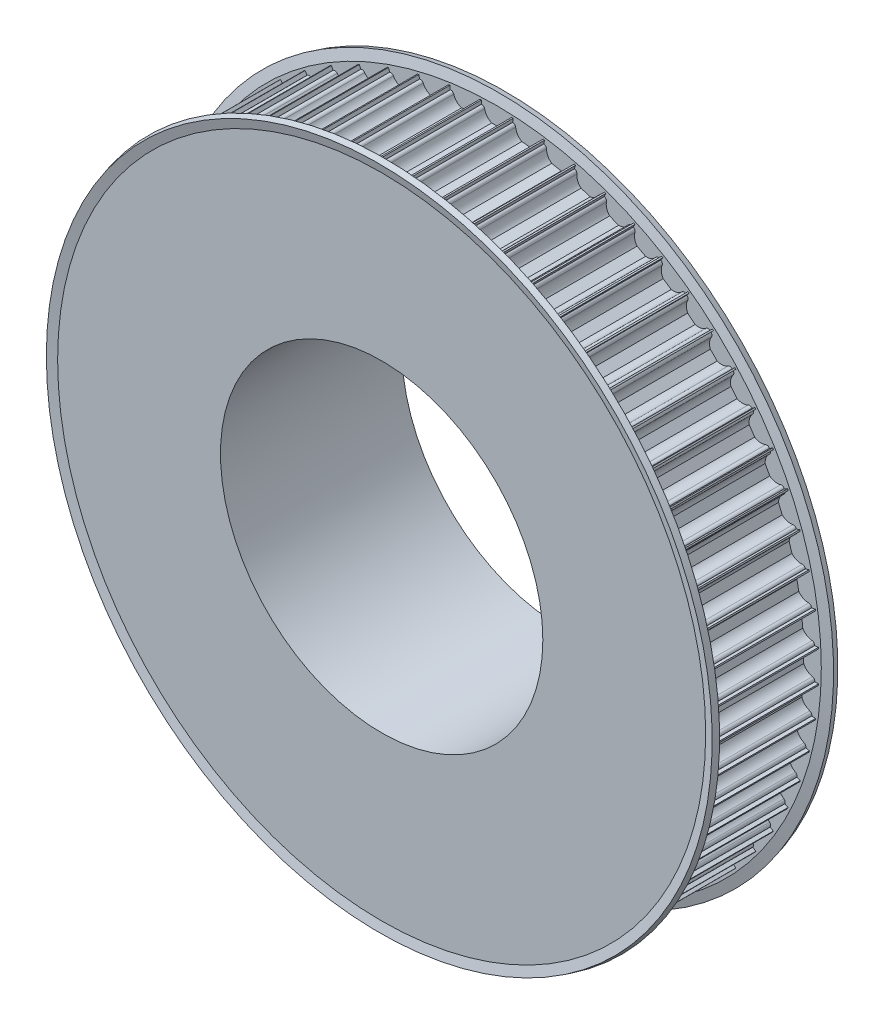
SolidWorks part; units mm, degrees
ref_plane "Front Plane" through (0, 0, 0) normal (0, 0, 1) x (1, 0, 0)
ref_plane "Top Plane" through (0, 0, 0) normal (0, 1, 0) x (1, 0, 0)
ref_plane "Right Plane" through (0, 0, 0) normal (1, 0, 0) x (0, 0, -1)
sketch "Sketch2" plane through (0, 0, 0) normal (1, 0, 0) x (0, 0, -1)
  line L0 (0, 0) -> (26.2549, 0) construction
  line L1 (0, 40) -> (45, 40)
  line L2 (45, 40) -> (45, 55.5)
  line L3 (45, 55.5) -> (30, 55.5)
  line L4 (30, 55.5) -> (30, 80)
  line L5 (30, 80) -> (0, 80)
  line L6 (0, 80) -> (0, 40)
  dimension "D1" = 80
  dimension "D2" = 40
  dimension "D3" = 30
  dimension "D4" = 15
  dimension "D5" = 15.5
revolve "Revolve1" add sketch "Sketch2" angle 360 about L0
sketch "Sketch3" plane through (0, 0, 0) normal (0, 0, 1) x (1, 0, 0)
  line L0 (-3.6742, 79) -> (-3.75, 79)
  line L1 (-3.75, 79) -> (-3.75, 81)
  line L2 (-3.75, 81) -> (3.75, 81)
  line L3 (3.75, 81) -> (3.75, 79)
  line L4 (3.75, 79) -> (3.6742, 79)
  line L5 (-1.199, 76.25) -> (1.199, 76.25)
  arc A0 (2.9394, 78.4) -> (1.199, 76.25) centre (0, 79) cw
  arc A1 (2.9394, 78.4) -> (3.6742, 79) centre (3.6742, 78.25) cw
  arc A2 (-2.9394, 78.4) -> (-3.6742, 79) centre (-3.6742, 78.25) ccw
  arc A3 (-1.199, 76.25) -> (-2.9394, 78.4) centre (0, 79) cw
  point P10 (0, 81)
  point P13 (3, 79)
  point P16 (-3, 79)
  dimension "D1" = 3
  dimension "D5" = 0.75
  dimension "D2" = 79
  dimension "D3" = 2
  dimension "D4" = 7.5
  dimension "D6" = 2.75
extrude "Cut-Extrude1" cut sketch "Sketch3" against normal up to next
pattern_circular "CirPattern1" count 64 over 360 about axis through (0, 0, 0) along (0, 0, 1) of "Cut-Extrude1"
sketch "Sketch4" plane through (0, 0, 0) normal (1, 0, 0) x (0, 0, -1)
  line L0 (15, -40.9775) -> (15, -19.0158) construction
  line L1 (30, -40.9775) -> (0, -40.9775) construction
  line L2 (30, -19.0158) -> (0, -19.0158) construction
  line L3 (30, 55.5) -> (30, 80.4125)
  line L4 (30, 80.4125) -> (30.592, 82.6218)
  line L5 (30.592, 82.6218) -> (29.1431, 83.01)
  line L6 (29.1431, 83.01) -> (28.5, 80.61)
  line L9 (28.5, 55.5) -> (30, 55.5)
  line L10 (28.5, 80.61) -> (28.5, 55.5)
  line L11 (45, 55.5) -> (30, 55.5) construction
  line L12 (1.5, 55.5) -> (0, 55.5)
  line L13 (1.5, 80.61) -> (1.5, 55.5)
  line L14 (-0.592, 82.6218) -> (0.8569, 83.01)
  line L15 (0.8569, 83.01) -> (1.5, 80.61)
  line L16 (0, 80.4125) -> (-0.592, 82.6218)
  line L17 (0, 55.5) -> (0, 80.4125)
  line L18 (0, 0) -> (-7.8265, 0) construction
  dimension "D1" = 15
  dimension "D2" = 1.5
  dimension "D3" = 25.11
  dimension "D4" = 2.4
revolve "Revolve2" add sketch "Sketch4" angle 360 about L18
